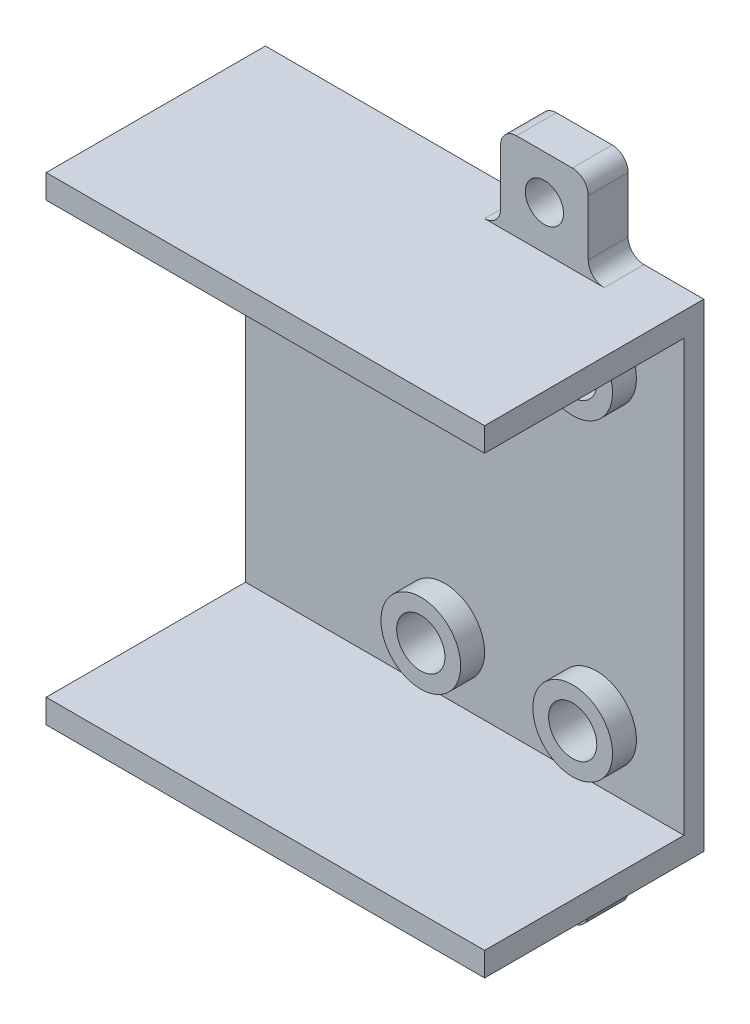
SolidWorks part; units mm, degrees
material "ABS"
ref_plane "X-Y Datum" through (0, 0, 0) normal (0, 0, 1) x (1, 0, 0)
ref_plane "X-Z Datum" through (0, 0, 0) normal (0, 1, 0) x (1, 0, 0)
ref_plane "Y-Z Datum" through (0, 0, 0) normal (1, 0, 0) x (0, 0, -1)
sketch "Sketch1" plane through (0, 0, 0) normal (0, 0, 1) x (1, 0, 0)
  line L1 (-27.5, 30) -> (27.5, 30)
  line L2 (-27.5, 30) -> (-27.5, -30)
  line L3 (-27.5, -30) -> (27.5, -30)
  line L4 (27.5, 30) -> (27.5, -30)
  line L5 (-27.5, 30) -> (27.5, -30) construction
  line L6 (-27.5, -30) -> (27.5, 30) construction
  point P0 (0, 0)
  dimension "D1" = 55
  dimension "D2" = 60
extrude "Boss-Extrude1" add sketch "Sketch1" along normal blind 2.5
sketch "Sketch2" plane through (0, 0, 2.5) normal (0, 0, 1) x (1, 0, 0)
  line L0 (27.5, -30) -> (27.5, 30) construction
  line L1 (-27.5, 30) -> (27.5, 30)
  line L2 (-27.5, 30) -> (-27.5, 27)
  line L3 (-27.5, 27) -> (27.5, 27)
  line L4 (27.5, 30) -> (27.5, 27)
  line L5 (-27.5, 30) -> (-27.5, -30) construction
  line L6 (27.5, -30) -> (-27.5, -30)
  line L7 (27.5, -30) -> (27.5, -27)
  line L8 (27.5, -27) -> (-27.5, -27)
  line L9 (-27.5, -30) -> (-27.5, -27)
  dimension "D1" = 3
extrude "Boss-Extrude2" add sketch "Sketch2" along normal blind 25
sketch "Sketch3" plane through (0, 0, 2.5) normal (0, 0, 1) x (1, 0, 0)
  circle A0 centre (-2.504, 19.6215) radius 3.025
  circle A1 centre (16.546, 19.6215) radius 3.025
  circle A2 centre (16.546, -19.6215) radius 3.025
  circle A3 centre (-2.504, -19.6215) radius 3.025
  circle A4 centre (-2.504, 19.6215) radius 5
  circle A5 centre (16.546, 19.6215) radius 5
  circle A6 centre (16.546, -19.6215) radius 5
  circle A7 centre (-2.504, -19.6215) radius 5
  dimension "D1" = 6.05
  dimension "D2" = 10
extrude "Boss-Extrude3" add sketch "Sketch3" along normal blind 3
sketch "Sketch4" plane through (0, 0, 2.5) normal (0, 0, 1) x (1, 0, 0)
  circle A0 centre (16.546, -19.6215) radius 3.025 construction
  circle A1 centre (-2.504, -19.6215) radius 3.025 construction
  circle A2 centre (16.546, 19.6215) radius 3.025 construction
  circle A3 centre (-2.504, 19.6215) radius 3.025 construction
  circle A4 centre (16.546, -19.6215) radius 3.025
  circle A5 centre (-2.504, -19.6215) radius 3.025
  circle A6 centre (16.546, 19.6215) radius 3.025
  circle A7 centre (-2.504, 19.6215) radius 3.025
extrude "Cut-Extrude1" cut sketch "Sketch4" against normal blind 2
sketch "Sketch5" plane through (0, 0, 0) normal (0, 0, -1) x (-1, 0, 0)
  line L0 (-27.5, 30) -> (27.5, 30) construction
  line L1 (-18, 30) -> (-7, 30)
  line L2 (-18, 30) -> (-18, 41)
  line L3 (-18, 41) -> (-7, 41)
  line L4 (-7, 30) -> (-7, 41)
  line L5 (-12.5, 41) -> (-12.5, 30)
  line L6 (-27.5, -30) -> (-27.5, 30) construction
  circle A0 centre (-12.5, 35.5) radius 2 construction
  line M9 (27.5, 30) -> (-27.5, 30)
  dimension "D3" = 4
  dimension "D1" = 11
  dimension "D2" = 11
  dimension "D4" = 15
extrude "Boss-Extrude4" add sketch "Sketch5" against normal blind 5 contours L3 L5 L4 M9 | L5 L3 L2 L1 region at (15.25, 35.5, 0) region at (9.75, 35.5, 0)
hole_wizard "M4 Clearance Hole1" positions "Sketch8" profile "Sketch7" hole size "M4" standard "ANSI Metric" end condition through all
sketch "Sketch8" plane through (0, 0, 5) normal (0, 0, 1) x (1, 0, 0)
  point P0 (12.5, 35.5)
sketch "Sketch7" plane through (12.5, 35.5, 5) normal (1, 0, 0) x (0, -1, 0)
  line L0 (0, 0) -> (0, 5)
  line L1 (0, 5) -> (2.4, 5)
  line L2 (2.4, 5) -> (2.4, 0)
  line L5 (2.4, 0) -> (0, 0)
  line L11 (0, -6.35) -> (0, 107.95) construction
  dimension "Thru Hole Dia." = 4.8
  dimension "Thru Hole Depth" = 5
sketch "Sketch9" plane through (0, 0, 5) normal (0, 0, 1) x (1, 0, 0)
  line L0 (12.5, 37.9) -> (18, 37.9)
  line L1 (12.5, 41) -> (12.5, 30) construction
  line L2 (18, 30) -> (18, 41) construction
  line L3 (12.5, 33.1) -> (18, 33.1)
  line L8 (18, 41) -> (7, 41)
  line L9 (7, 41) -> (7, 30)
  line L10 (7, 30) -> (18, 30)
  line L11 (18, 30) -> (18, 41)
  line L12 (18, 41) -> (7, 41)
  line L13 (7, 41) -> (7, 30)
  line L14 (7, 30) -> (18, 30)
  line L15 (18, 30) -> (18, 41)
  circle A0 centre (12.5, 35.5) radius 2.4 construction
  circle A1 centre (12.5, 35.5) radius 2.4
  circle M5 centre (12.5, 35.5) radius 2.4
  line M9 (18, 30) -> (18, 41)
  dimension "D1" = 0
extrude "Cut-Extrude2" [suppressed] cut sketch "Sketch9" against normal through all contours L3 L0 M5 M9
mirror "Mirror2" about plane through (0, 0, 0) normal (0, 1, 0) of "Cut-Extrude2", "M4 Clearance Hole1", "Boss-Extrude4"
fillet "Fillet2" [suppressed] radius 2
fillet "Fillet3" radius 2 8 edges at (18, -30, 2.5) (18, -41, 2.5) (7, -41, 2.5) (7, -30, 2.5) (18, 30, 2.5) (18, 41, 2.5) (7, 41, 2.5) (7, 30, 2.5)
